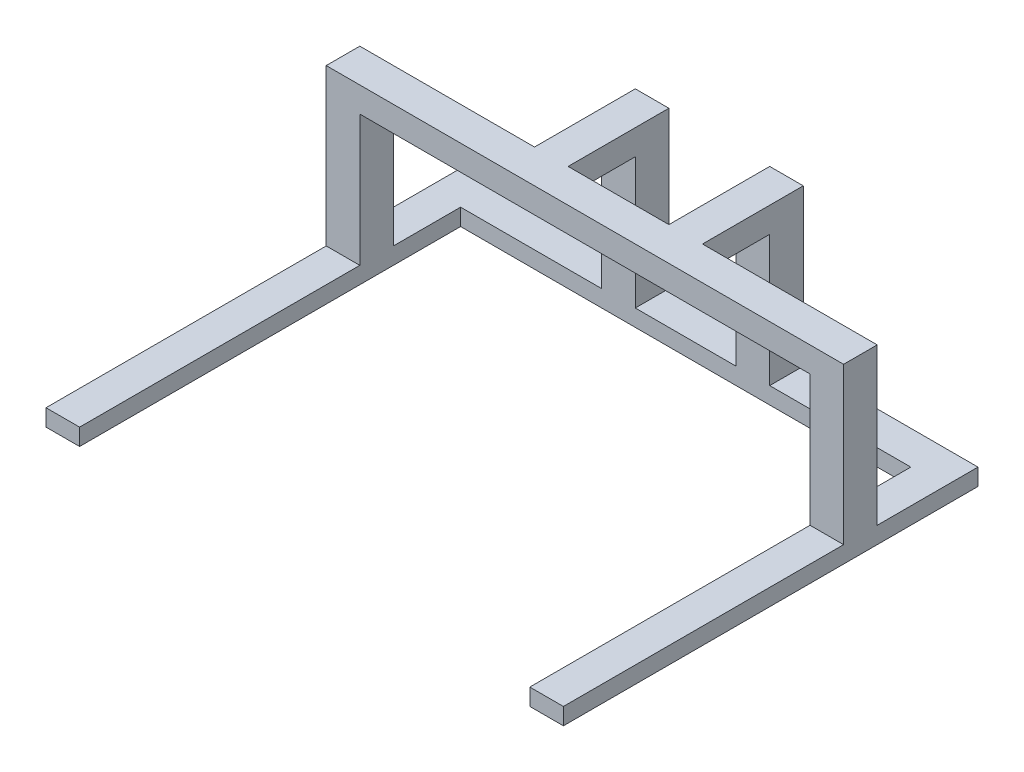
SolidWorks part; units mm, degrees
material "PUR"
ref_plane "Front Plane" through (0, 0, 0) normal (0, 0, 1) x (1, 0, 0)
ref_plane "Top Plane" through (0, 0, 0) normal (0, 1, 0) x (1, 0, 0)
ref_plane "Right Plane" through (0, 0, 0) normal (1, 0, 0) x (0, 0, -1)
sketch "Sketch1" plane through (0, 0, 0) normal (0, 1, 0) x (1, 0, 0)
  line L1 (-48.895, -3.175) -> (48.895, -3.175)
  line L2 (-48.895, -3.175) -> (-48.895, 3.175)
  line L3 (-48.895, 3.175) -> (48.895, 3.175)
  line L4 (48.895, -3.175) -> (48.895, 3.175)
  line L5 (-48.895, -3.175) -> (48.895, 3.175) construction
  line L6 (-48.895, 3.175) -> (48.895, -3.175) construction
  line L7 (-48.895, 3.175) -> (-42.545, 3.175)
  line L8 (-48.895, 3.175) -> (-48.895, -3.175)
  line L9 (-48.895, -3.175) -> (-42.545, -3.175)
  line L10 (-42.545, 3.175) -> (-42.545, -3.175)
  line L11 (48.895, 3.175) -> (42.545, 3.175)
  line L12 (48.895, 3.175) -> (48.895, -3.175)
  line L13 (48.895, -3.175) -> (42.545, -3.175)
  line L14 (42.545, 3.175) -> (42.545, -3.175)
  line L19 (-15.875, 3.175) -> (-9.525, 3.175)
  line L20 (-15.875, 3.175) -> (-15.875, 22.225)
  line L21 (-15.875, 22.225) -> (-9.525, 22.225)
  line L22 (-9.525, 3.175) -> (-9.525, 22.225)
  line L23 (-15.875, 22.225) -> (-9.525, 22.225)
  line L24 (-15.875, 22.225) -> (-15.875, 15.875)
  line L25 (-15.875, 15.875) -> (-9.525, 15.875)
  line L26 (-9.525, 22.225) -> (-9.525, 15.875)
  point P0 (0, 0)
  dimension "D1" = 85.09
  dimension "D2" = 6.35
  dimension "D3" = 6.35
  dimension "D4" = 6.35
  dimension "D5" = 6.35
  dimension "D6" = 9.525
  dimension "D7" = 19.05
  dimension "D8" = 6.35
extrude "Boss-Extrude1" add sketch "Sketch1" along normal blind 4.7625 contours L14 L3 L10 L1 | L8 L7 L10 L9 | L12 L11 L14 L13 | L20 L19 L22 L21 region at (0, 0, 0)
extrude "Boss-Extrude2" add sketch "Sketch1<3>" against normal blind 27.94 contours L10 L3 L2 L1 | L3 L14 L1 L4 | L24 L23 L26 L25 region at (-45.72, 0, 0) region at (45.72, 0, 0)
sketch "Sketch1<3>" plane through (0, 0, 0) normal (0, 1, 0) x (1, 0, 0) same geometry as "Sketch1"
mirror "Mirror1" about plane through (0, 0, 0) normal (1, 0, 0) of bodies 102
sketch "Sketch2" plane through (0, -27.94, 0) normal (0, -1, 0) x (1, 0, 0)
  line L0 (9.525, -22.225) -> (9.525, -15.875) construction
  line L1 (-9.525, -15.875) -> (9.525, -15.875)
  line L2 (-9.525, -15.875) -> (-9.525, -22.225)
  line L3 (-9.525, -22.225) -> (9.525, -22.225)
  line L4 (9.525, -15.875) -> (9.525, -22.225)
  line L5 (-15.875, -22.225) -> (-9.525, -22.225) construction
  line L6 (0, 0) -> (0, -37.3923) construction
  line L11 (-48.895, 3.175) -> (-48.895, -22.225)
  line L12 (-48.895, -22.225) -> (-15.875, -22.225)
  line L13 (-15.875, -22.225) -> (-9.525, -22.225) construction
  line L14 (-15.875, -22.225) -> (-15.875, -15.875)
  line L15 (-15.875, -15.875) -> (-9.525, -15.875) construction
  line L16 (-48.895, 3.175) -> (-42.545, 3.175)
  line L17 (-42.545, 3.175) -> (-42.545, -15.875)
  line L18 (-42.545, -15.875) -> (-15.875, -15.875)
  line L19 (42.545, 3.175) -> (42.545, -15.875)
  line L20 (48.895, 3.175) -> (42.545, 3.175)
  line L21 (48.895, 3.175) -> (48.895, -22.225)
  line L22 (48.895, -22.225) -> (15.875, -22.225)
  line L23 (15.875, -22.225) -> (15.875, -15.875)
  line L24 (42.545, -15.875) -> (15.875, -15.875)
extrude "Boss-Extrude3" add sketch "Sketch2" against normal blind 3.175 contours L6 L1 L2 L3 | L6 L3 | L6 L3 | L18 L14 L12 L11 L16 L17 | L19 L24 L23 L22 L21 L20 region at (0, -27.94, -19.05)
fillet "Fillet1" [suppressed] radius 5.08
fillet "Fillet2" [suppressed] radius 5.08
sketch "Sketch3" plane through (0, -27.94, 0) normal (0, -1, 0) x (1, 0, 0)
  line L1 (-48.895, 3.175) -> (-42.545, 3.175)
  line L2 (-48.895, 3.175) -> (-48.895, 56.134)
  line L3 (-48.895, 56.134) -> (-42.545, 56.134)
  line L4 (-42.545, 3.175) -> (-42.545, 56.134)
  dimension "D1" = 6.35
  dimension "D2" = 52.959
extrude "Boss-Extrude4" add sketch "Sketch3" against normal blind 3.175
mirror "Mirror2" about plane through (0, 0, 0) normal (1, 0, 0) of "Boss-Extrude4"
